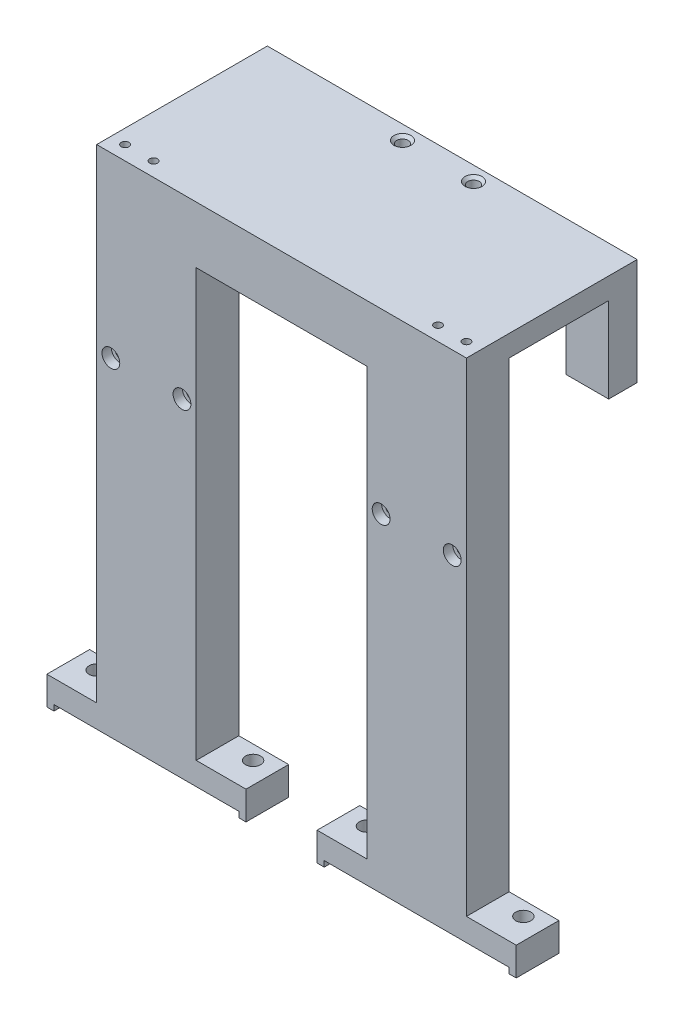
SolidWorks part; units mm, degrees
material "6061 Alloy"
ref_plane "Front Plane" through (0, 0, 0) normal (0, 0, 1) x (1, 0, 0)
ref_plane "Top Plane" through (0, 0, 0) normal (0, 1, 0) x (1, 0, 0)
ref_plane "Right Plane" through (0, 0, 0) normal (1, 0, 0) x (0, 0, -1)
sketch "Sketch1" plane through (0, 0, 0) normal (0, 0, 1) x (1, 0, 0)
  line L1 (-82.55, -114.3) -> (82.55, -114.3)
  line L2 (-82.55, -114.3) -> (-82.55, 114.3)
  line L3 (-82.55, 114.3) -> (82.55, 114.3)
  line L4 (82.55, -114.3) -> (82.55, 114.3)
  line L5 (-82.55, -114.3) -> (82.55, 114.3) construction
  line L6 (-82.55, 114.3) -> (82.55, -114.3) construction
  point P0 (0, 0)
  dimension "D1" = 228.6
  dimension "D2" = 165.1
extrude "Boss-Extrude1" add sketch "Sketch1" along normal blind 19.05
sketch "Sketch2" plane through (0, 0, 19.05) normal (0, 0, 1) x (1, 0, 0)
  line L0 (-82.55, -114.3) -> (82.55, -114.3) construction
  line L1 (-38.1, -114.3) -> (38.1, -114.3)
  line L2 (-38.1, -114.3) -> (-38.1, 88.9)
  line L3 (-38.1, 88.9) -> (38.1, 88.9)
  line L4 (38.1, -114.3) -> (38.1, 88.9)
  line L5 (-82.55, 114.3) -> (-82.55, -114.3) construction
  dimension "D1" = 203.2
  dimension "D2" = 76.2
  dimension "D3" = 44.45
extrude "Cut-Extrude1" cut sketch "Sketch2" against normal through all
sketch "Sketch3" plane through (0, 0, 0) normal (0, 0, -1) x (-1, 0, 0)
  line L0 (82.55, 114.3) -> (82.55, -114.3) construction
  line L1 (-82.55, 114.3) -> (82.55, 114.3)
  line L2 (-82.55, 114.3) -> (-82.55, 104.775)
  line L3 (-82.55, 104.775) -> (82.55, 104.775)
  line L4 (82.55, 114.3) -> (82.55, 104.775)
  dimension "D1" = 9.525
extrude "Boss-Extrude2" add sketch "Sketch3" along normal blind 57.15
sketch "Sketch4" plane through (0, 0, -57.15) normal (0, 0, -1) x (-1, 0, 0)
  line L7 (-82.55, 104.775) -> (-63.5, 104.775)
  line L8 (-82.55, 104.775) -> (-82.55, 66.675)
  line L9 (-82.55, 66.675) -> (-63.5, 66.675)
  line L10 (-63.5, 104.775) -> (-63.5, 66.675)
  dimension "D1" = 38.1
  dimension "D2" = 19.05
extrude "Boss-Extrude3" add sketch "Sketch4" against normal blind 12.7
mirror "Mirror1" about plane through (0, 0, 0) normal (1, 0, 0) of "Boss-Extrude3"
sketch "Sketch7" plane through (0, 0, 19.05) normal (0, 0, 1) x (1, 0, 0)
  line L0 (-82.55, -114.3) -> (-38.1, -114.3) construction
  line L1 (-104.775, -101.6) -> (-15.875, -101.6)
  line L2 (-104.775, -101.6) -> (-104.775, -114.3)
  line L3 (-104.775, -114.3) -> (-15.875, -114.3)
  line L4 (-15.875, -101.6) -> (-15.875, -114.3)
  line L5 (-104.775, -101.6) -> (-15.875, -114.3) construction
  line L6 (-104.775, -114.3) -> (-15.875, -101.6) construction
  line L7 (-82.55, 114.3) -> (-82.55, -114.3) construction
  point P0 (-60.325, -107.95)
  dimension "D1" = 0
  dimension "D2" = 88.9
  dimension "D3" = 22.225
  dimension "D4" = 12.7
extrude "Boss-Extrude4" add sketch "Sketch7" against normal blind 19.05
sketch "Sketch8" plane through (0, -114.3, 0) normal (0, -1, 0) x (-1, 0, 0)
  line L0 (104.775, -19.05) -> (15.875, -19.05) construction
  line L1 (101.6, 0) -> (19.05, 0)
  line L2 (101.6, 0) -> (101.6, -19.05)
  line L3 (101.6, -19.05) -> (19.05, -19.05)
  line L4 (19.05, 0) -> (19.05, -19.05)
  line L5 (101.6, 0) -> (19.05, -19.05) construction
  line L6 (101.6, -19.05) -> (19.05, 0) construction
  line L8 (104.775, 0) -> (104.775, -19.05) construction
  line L9 (15.875, 0) -> (15.875, -19.05) construction
  point P0 (60.325, -9.525)
  dimension "D1" = 19.05
  dimension "D2" = 3.175
  dimension "D3" = 3.175
extrude "Cut-Extrude4" cut sketch "Sketch8" against normal blind 2.54
mirror "Mirror3" about plane through (0, 0, 0) normal (1, 0, 0) of "Cut-Extrude4", "Boss-Extrude4"
hole_wizard "#8-32 Tapped Hole1" positions "Sketch11" profile "Sketch10" tap size "#8-32" standard "ANSI Inch"
sketch "Sketch11" plane through (0, 114.3, 0) normal (0, 1, 0) x (1, 0, 0)
  line L0 (-82.55, 0) -> (-82.55, -19.05) construction
  line L1 (-82.55, -19.05) -> (-82.55, 57.15) construction
  line L2 (82.55, 0) -> (82.55, -19.05) construction
  line L3 (82.55, -19.05) -> (82.55, 57.15) construction
  line L4 (82.55, -19.05) -> (-82.55, -19.05) construction
  point P0 (-76.2, -12.7)
  point P2 (-63.5, -12.7)
  point P4 (63.5, -12.7)
  point P6 (76.2, -12.7)
  dimension "D1" = 6.35
  dimension "D2" = 19.05
  dimension "D3" = 6.35
  dimension "D4" = 19.05
  dimension "D5" = 6.35
  dimension "D6" = 6.35
  dimension "D7" = 6.35
  dimension "D8" = 6.35
cosmetic thread "Hole Thread1" parameters "D1"=3.048, "D2"=4.1656
cosmetic thread "Hole Thread2" parameters "D1"=3.048, "D2"=4.1656
cosmetic thread "Hole Thread3" parameters "D1"=3.048, "D2"=4.1656
cosmetic thread "Hole Thread4" parameters "D1"=3.048, "D2"=4.1656
sketch "Sketch10" plane through (-76.2, 114.3, 12.7) normal (1, 0, 0) x (0, 0, 1)
  line L0 (0, 0) -> (0, 13.7378)
  line L1 (0, 13.7378) -> (1.7272, 12.7)
  line L2 (1.7272, 12.7) -> (1.7272, 0)
  line L5 (1.7272, 0) -> (0, 0)
  line L10 (0, 13.7378) -> (-1.7272, 12.7) construction
  line L11 (0, -6.35) -> (0, 107.95) construction
  dimension "Tap Drill Dia." = 3.4544
  dimension "Tap Drill Depth" = 12.7
  dimension "Drill Angle" = 118
hole_wizard "1/4 Clearance Hole1" positions "Sketch12" profile "Sketch13" hole size "1/4" standard "ANSI Inch" end condition up to next
sketch "Sketch12" plane through (0, -101.6, 0) normal (0, 1, 0) x (1, 0, 0)
  line L0 (-104.775, 0) -> (-104.775, -19.05) construction
  line L1 (-82.55, 0) -> (-104.775, 0) construction
  line L2 (-15.875, 0) -> (-38.1, 0) construction
  line L3 (-15.875, 0) -> (-15.875, -19.05) construction
  line L4 (15.875, 0) -> (15.875, -19.05) construction
  line L5 (15.875, 0) -> (38.1, 0) construction
  line L6 (82.55, 0) -> (104.775, 0) construction
  line L7 (104.775, 0) -> (104.775, -19.05) construction
  point P0 (-95.25, -6.35)
  point P2 (-25.4, -6.35)
  point P4 (25.4, -6.35)
  point P6 (95.25, -6.35)
  dimension "D1" = 9.525
  dimension "D2" = 6.35
  dimension "D3" = 6.35
  dimension "D4" = 9.525
  dimension "D5" = 9.525
  dimension "D6" = 6.35
  dimension "D7" = 6.35
  dimension "D8" = 9.525
sketch "Sketch13" plane through (-95.25, -101.6, 6.35) normal (1, 0, 0) x (0, 0, 1)
  line L0 (0, 0) -> (0, 10.16)
  line L1 (0, 10.16) -> (3.3782, 10.16)
  line L2 (3.3782, 10.16) -> (3.3782, 0)
  line L5 (3.3782, 0) -> (0, 0)
  line L11 (0, -6.35) -> (0, 107.95) construction
  dimension "Thru Hole Dia." = 6.7564
  dimension "Thru Hole Depth" = 10.16
hole_wizard "CBORE for #8 Socket Head Cap Screw1" positions "Sketch18" profile "Sketch19" counterbore size "#8" standard "ANSI Inch" end condition up to next
sketch "Sketch18" plane through (0, 0, 19.05) normal (0, 0, 1) x (1, 0, 0)
  line L0 (-82.55, 114.3) -> (-82.55, -101.6) construction
  line L1 (-38.1, 88.9) -> (-38.1, -101.6) construction
  line L2 (38.1, -101.6) -> (38.1, 88.9) construction
  line L3 (82.55, -101.6) -> (82.55, 114.3) construction
  point P0 (-76.2, 34.925)
  point P2 (-44.45, 34.925)
  point P4 (44.45, 34.925)
  point P6 (76.2, 34.925)
  dimension "D1" = 6.35
  dimension "D2" = 6.35
  dimension "D3" = 6.35
  dimension "D4" = 6.35
  dimension "D5" = 136.525
  dimension "D6" = 136.525
  dimension "D7" = 136.525
  dimension "D8" = 136.525
sketch "Sketch19" plane through (-76.2, 34.925, 19.05) normal (1, 0, 0) x (0, -1, 0)
  line L0 (0, 0) -> (0, 19.05)
  line L1 (0, 19.05) -> (2.2479, 19.05)
  line L3 (2.2479, 19.05) -> (2.2479, 4.1656)
  line L4 (2.2479, 4.1656) -> (3.9687, 4.1656)
  line L5 (3.9687, 4.1656) -> (3.9687, 0)
  line L7 (3.9687, 0) -> (0, 0)
  line L11 (0, -6.35) -> (0, 107.95) construction
  dimension "Thru Hole Dia." = 4.4958
  dimension "Thru Hole Depth" = 19.05
  dimension "C'Bore Dia." = 7.9375
  dimension "C'Bore Depth" = 4.1656
hole_wizard "1/4-20 Tapped Hole1" positions "Sketch20" profile "Sketch21" tap size "1/4-20" standard "ANSI Inch" end condition through all
sketch "Sketch20" plane through (0, 114.3, 0) normal (0, 1, 0) x (1, 0, 0)
  line L0 (-82.55, -19.05) -> (-82.55, 57.15) construction
  line L1 (82.55, -19.05) -> (82.55, 57.15) construction
  line L2 (-82.55, 57.15) -> (82.55, 57.15) construction
  point P0 (15.875, 50.8)
  point P2 (-15.875, 50.8)
  dimension "D1" = 66.675
  dimension "D2" = 66.675
  dimension "D3" = 6.35
  dimension "D4" = 6.35
sketch "Sketch21" plane through (15.875, 114.3, -50.8) normal (1, 0, 0) x (0, 0, 1)
  line L0 (0, 0) -> (0, 228.6)
  line L1 (0, 228.6) -> (2.5527, 228.6)
  line L2 (2.5527, 228.6) -> (2.5527, 1.2573)
  line L3 (2.5527, 1.2573) -> (3.81, 0)
  line L5 (3.81, 0) -> (0, 0)
  line L6 (-2.5527, 1.2573) -> (-3.81, 0) construction
  line L11 (0, -6.35) -> (0, 107.95) construction
  dimension "Thru Tap Drill Dia." = 5.1054
  dimension "Thru Tap Drill Depth" = 228.6
  dimension "Near C'Sink Dia." = 7.62
  dimension "Near C'Sink Angle" = 90
cosmetic thread "Hole Thread5" parameters "D2"=6.35
cosmetic thread "Hole Thread6" parameters "D2"=6.35
sketch "Sketch22" plane through (0, 0, -57.15) normal (0, 0, -1) x (-1, 0, 0)
  line L0 (-63.5, 104.775) -> (63.5, 104.775) construction
  line L1 (3.175, 98.425) -> (-3.175, 98.425)
  line L2 (3.175, 98.425) -> (3.175, 104.775)
  line L3 (3.175, 104.775) -> (-3.175, 104.775)
  line L4 (-3.175, 98.425) -> (-3.175, 104.775)
  line L5 (3.175, 98.425) -> (-3.175, 104.775) construction
  line L6 (3.175, 104.775) -> (-3.175, 98.425) construction
  point P0 (0, 101.6)
  dimension "D1" = 6.35
  dimension "D2" = 6.35
  dimension "D3" = 0
extrude "Boss-Extrude5" add sketch "Sketch22" along normal blind 3.175 from offset 7.9375 separate body offset against normal yes
sketch "Sketch23" plane through (0, 0, -52.3875) normal (0, 0, -1) x (-1, 0, 0)
  line L0 (-3.175, 98.425) -> (3.175, 98.425) construction
  line L1 (-3.175, 104.775) -> (-3.175, 98.425) construction
  circle A0 centre (0, 101.6) radius 1.5875
  dimension "D3" = 3.175
  dimension "D1" = 3.175
  dimension "D2" = 3.175
extrude "Cut-Extrude5" cut sketch "Sketch23" against normal up to next (3.175 mm away)
